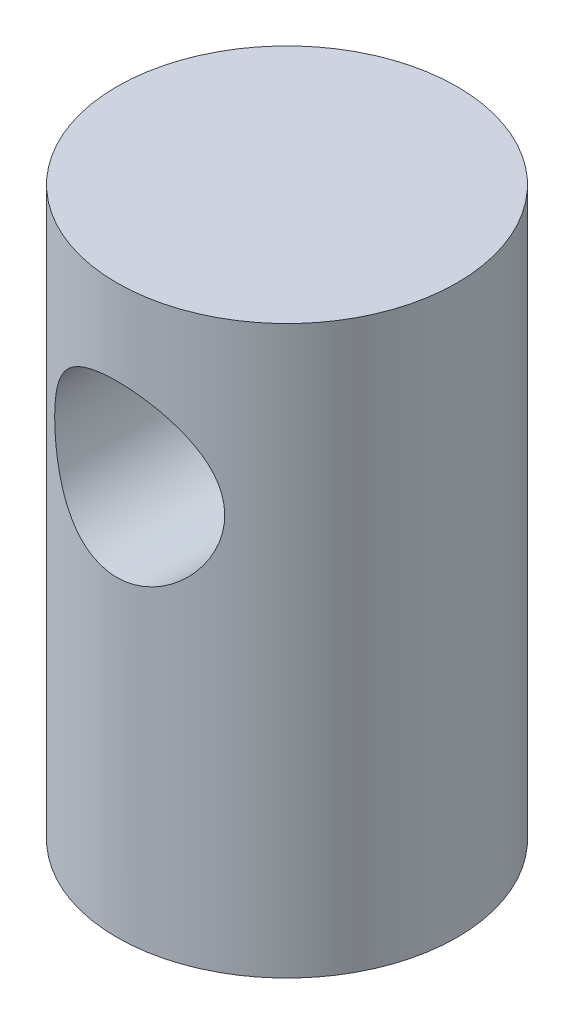
SolidWorks part; units mm, degrees
ref_plane "Front Plane" through (0, 0, 0) normal (0, 0, 1) x (1, 0, 0)
ref_plane "Top Plane" through (0, 0, 0) normal (0, 1, 0) x (1, 0, 0)
ref_plane "Right Plane" through (0, 0, 0) normal (1, 0, 0) x (0, 0, -1)
sketch "Sketch1" plane through (0, 0, 0) normal (0, 1, 0) x (1, 0, 0)
  circle A0 centre (0, 0) radius 3.81
  dimension "D1" = 7.62
extrude "Boss-Extrude1" add sketch "Sketch1" along normal blind 12.7 contours A0
sketch "Sketch2" plane through (0, 0, 0) normal (0, 0, 1) x (1, 0, 0)
  line L0 (3.81, 12.7) -> (-3.81, 12.7) construction
  circle A0 centre (0, 8.89) radius 1.905
  point P0 (0, 9.8348)
  dimension "D1" = 3.81
  dimension "D2" = 3.81
extrude "Cut-Extrude1" cut sketch "Sketch2" against normal up to surface and the other way blind 19.05 up to face at (0, 12.7, 3.81)
sketch "Sketch6" plane through (0, 0, 0) normal (0, 0, 1) x (1, 0, 0)
  line L0 (0, 12.7) -> (0, 0) construction
  line L1 (3.81, 12.7) -> (-3.81, 12.7) construction
